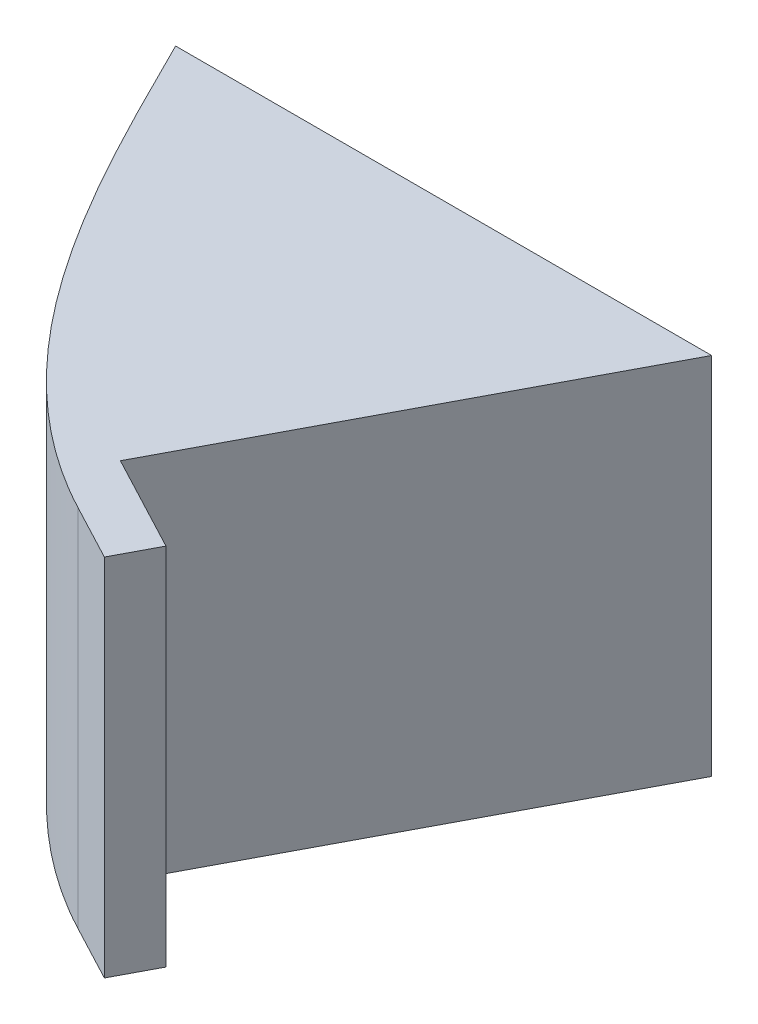
SolidWorks part; units mm, degrees
ref_plane "Front Plane" through (0, 0, 0) normal (0, 0, 1) x (1, 0, 0)
ref_plane "Top Plane" through (0, 0, 0) normal (0, 1, 0) x (1, 0, 0)
ref_plane "Right Plane" through (0, 0, 0) normal (1, 0, 0) x (0, 0, -1)
sketch "Sketch1" plane through (0, 0, 0) normal (0, 1, 0) x (1, 0, 0)
  line L0 (-27.2615, 0) -> (31.5506, 0)
  line L1 (31.5506, 0) -> (9.1186, -42.4359)
  line L2 (9.1186, -42.4359) -> (19.7276, -48.0439)
  line L3 (19.7276, -48.0439) -> (17.391, -52.4643)
  line L4 (17.391, -52.4643) -> (11.2063, -49.1951)
  spline S0 degree 3 poles (11.2063, -49.1951) (-8.0343, -39.0243) (-18.2233, -18.1649) (-27.2615, 0) knots 0 0 0 0 1 1 1 1
  spline S1 degree 3 poles (9.1186, -42.4359) (5.8536, -40.71) (-5.5564, -31.0745) (9.4719, -8.0193) (8.4116, 0) knots 0 0 0 0 0.194742 1 1 1 1 construction
  dimension "D1" = 48
  dimension "D2" = 12
  dimension "D3" = 5
extrude "Boss-Extrude1" add sketch "Sketch1" along normal blind 40
sketch "Sketch2" plane through (0, 0, 0) normal (0, 0, -1) x (-1, 0, 0)
  line L0 (-31.5506, 0) -> (27.2615, 0) construction
  line L1 (23.2615, 36) -> (-8.7385, 36) construction
  line L2 (-8.7385, 36) -> (-8.7385, 4) construction
  line L3 (-8.7385, 4) -> (23.2615, 4) construction
  line L4 (23.2615, 4) -> (23.2615, 36) construction
  line L5 (-31.5506, 40) -> (27.2615, 40) construction
  line L6 (27.2615, 40) -> (27.2615, 0) construction
  circle A0 centre (7.2615, 20) radius 20 construction
  circle A1 centre (7.2615, 20) radius 19 construction
  circle A2 centre (7.2615, 20) radius 16 construction
  circle A3 centre (23.2615, 36) radius 1.5
  circle A4 centre (23.2615, 4) radius 1.5
  circle A5 centre (-8.7385, 4) radius 1.5
  circle A6 centre (-8.7385, 36) radius 1.5
  dimension "D2" = 38
  dimension "D3" = 3
  dimension "D1" = 32
